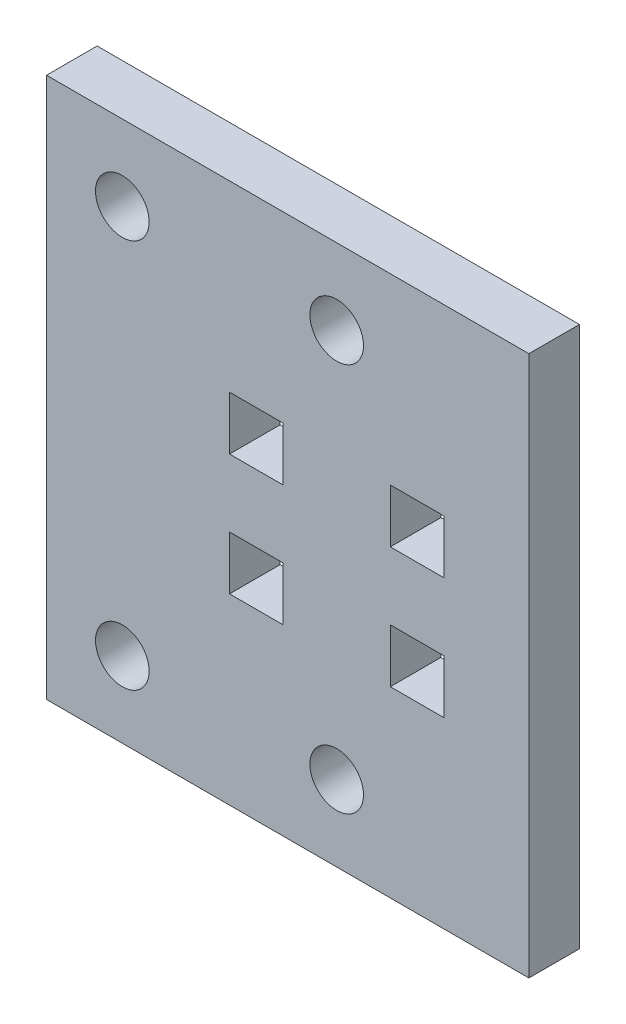
SolidWorks part; units mm, degrees
ref_plane "Front Plane" through (0, 0, 0) normal (0, 0, 1) x (1, 0, 0)
ref_plane "Top Plane" through (0, 0, 0) normal (0, 1, 0) x (1, 0, 0)
ref_plane "Right Plane" through (0, 0, 0) normal (1, 0, 0) x (0, 0, -1)
sketch "Sketch1" plane through (0, 0, 0) normal (0, 0, 1) x (-1, 0, 0)
  line L8 (62.1098, 30.6992) -> (62.1098, -33.3613)
  line L9 (62.1098, -33.3613) -> (4.9598, -33.3613)
  line L10 (4.9598, -33.3613) -> (4.9598, 30.6992)
  line L11 (4.9598, 30.6992) -> (62.1098, 30.6992)
  line L36 (15.0296, 2.6689) -> (15.0296, 9.0189)
  line L37 (15.0296, 9.0189) -> (21.3796, 9.0189)
  line L38 (15.0296, 2.6689) -> (21.3796, 2.6689)
  line L40 (40.4296, -5.3311) -> (40.4296, -11.6811)
  line L41 (34.0796, -5.3311) -> (40.4296, -5.3311)
  line L42 (34.0796, -11.6811) -> (40.4296, -11.6811)
  line L43 (34.0796, -5.3311) -> (34.0796, -11.6811)
  line L45 (21.3796, 2.6689) -> (21.3796, 9.0189)
  line L47 (21.3796, -5.3311) -> (21.3796, -11.6811)
  line L49 (34.0796, 2.6689) -> (34.0796, 9.0189)
  line L50 (34.0796, 9.0189) -> (40.4296, 9.0189)
  line L53 (34.0796, 2.6689) -> (40.4296, 2.6689)
  line L55 (15.0296, -5.3311) -> (21.3796, -5.3311)
  line L57 (40.4296, 2.6689) -> (40.4296, 9.0189)
  line L59 (15.0296, -11.6811) -> (21.3796, -11.6811)
  line L63 (15.0296, -5.3311) -> (15.0296, -11.6811)
  circle A0 centre (53.1296, -24.3811) radius 3.175
  circle A1 centre (53.1296, 21.7189) radius 3.175
  circle A2 centre (27.7296, -24.3811) radius 3.175
  circle A3 centre (27.7296, 21.7189) radius 3.175
extrude "Boss-Extrude1" add sketch "Sketch1" along normal blind 5.9944
